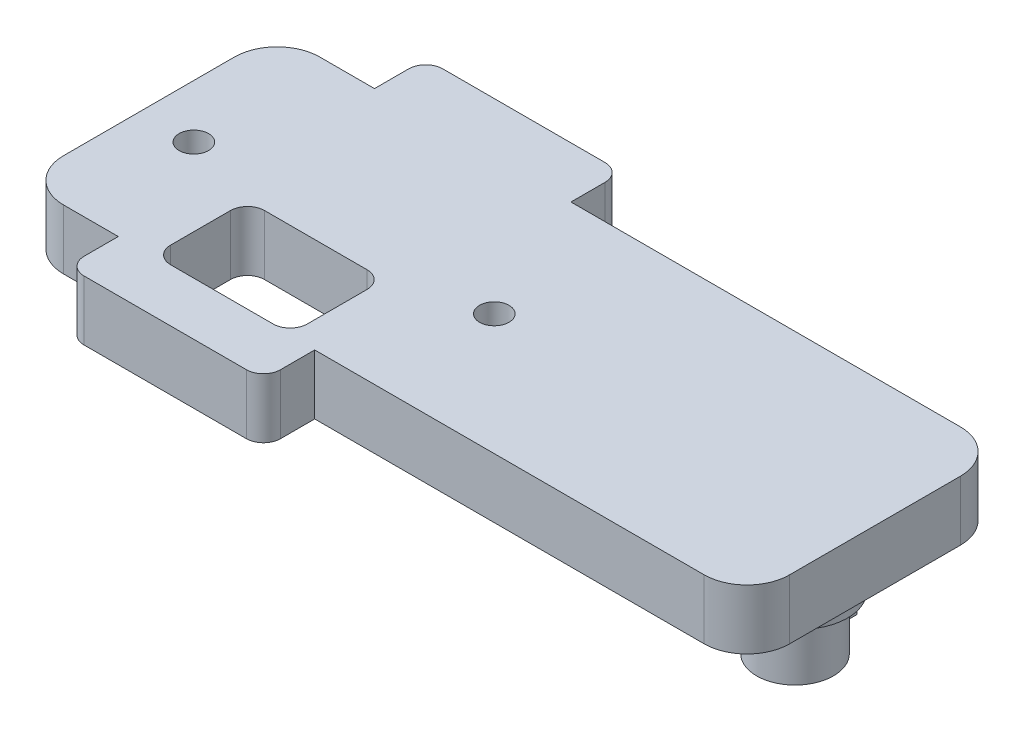
SolidWorks part; units mm, degrees
ref_plane "Front Plane" through (0, 0, 0) normal (0, 0, 1) x (1, 0, 0)
ref_plane "Top Plane" through (0, 0, 0) normal (0, 1, 0) x (1, 0, 0)
ref_plane "Right Plane" through (0, 0, 0) normal (1, 0, 0) x (0, 0, -1)
sketch "Sketch1" plane through (0, 0, 0) normal (0, 1, 0) x (1, 0, 0)
  line L1 (-33.413, 19.2228) -> (51.587, 19.2228)
  line L2 (-33.413, 19.2228) -> (-33.413, -10.7772)
  line L3 (-33.413, -10.7772) -> (51.587, -10.7772)
  line L4 (51.587, 19.2228) -> (51.587, -10.7772)
  dimension "D1" = 85
  dimension "D2" = 30
extrude "Boss-Extrude1" add sketch "Sketch1" along normal blind 7
ref_plane "Plane1" through (0, -1, 0) normal (0, -1, 0) x (-1, 0, 0)
sketch "Sketch2" plane through (0, -1, 0) normal (0, -1, 0) x (-1, 0, 0)
  line L0 (-51.587, 4.2228) -> (57.5711, 4.2228) construction
  line L1 (-41.1646, 1.3228) -> (-44.5646, 1.3228)
  line L2 (-41.1646, 1.3228) -> (-41.1646, 7.1228)
  line L3 (-41.1646, 7.1228) -> (-44.5646, 7.1228)
  line L4 (-44.5646, 1.3228) -> (-44.5646, 7.1228)
  line L5 (-51.587, -10.7772) -> (-51.587, 19.2228) construction
  line L6 (-42.8646, -10.7772) -> (-42.8646, 27.765) construction
  line L8 (33.413, -10.7772) -> (-51.587, -10.7772) construction
  dimension "D1" = 3.4
  dimension "D2" = 5.8
  dimension "D3" = 1.7
  dimension "D4" = 2.9
extrude "Boss-Extrude2" add sketch "Sketch2" along normal blind 6 separate body
shell "Shell1" thickness 1 removed face at (42.8646, -7, -4.2228) outward yes
sketch "Sketch3" plane through (0, 0, 0) normal (0, -1, 0) x (-1, 0, 0)
  line L0 (-42.8646, 1.3228) -> (-42.8646, 11.0227) construction
  line L1 (-44.5646, 1.3228) -> (-41.1646, 1.3228) construction
  line L2 (-41.1646, 4.2228) -> (-49.8164, 4.2228) construction
  line L3 (-41.1646, 1.3228) -> (-41.1646, 7.1228) construction
  point P9 (-42.8646, 4.2228)
sketch "Sketch4" plane through (0, 0, 0) normal (0, -1, 0) x (-1, 0, 0)
  circle A0 centre (-42.9099, 3.5376) radius 4.5
  circle A1 centre (-42.9099, 3.5376) radius 3.7
extrude "Boss-Extrude3" add sketch "Sketch4" along normal blind 10
sketch "Sketch5" plane through (0, 0, 0) normal (0, -1, 0) x (-1, 0, 0)
  circle A0 centre (-42.8646, 4.2228) radius 4.25
  circle A1 centre (-42.8646, 4.2228) radius 5.5
extrude "Boss-Extrude4" add sketch "Sketch5" along normal blind 4
fillet "Fillet1" radius 5 4 edges at (-33.413, 3.5, -19.2228) (-33.413, 3.5, 10.7772) (51.587, 3.5, -19.2228) (51.587, 3.5, 10.7772)
sketch "Sketch6" plane through (0, 0, 0) normal (0, -1, 0) x (-1, 0, 0)
  line L0 (28.413, -10.7772) -> (-46.587, -10.7772) construction
  line L1 (22.0125, -10.7772) -> (-0.9875, -10.7772)
  line L2 (22.0125, -10.7772) -> (22.0125, -16.7772)
  line L3 (22.0125, -16.7772) -> (-0.9875, -16.7772)
  line L4 (-0.9875, -10.7772) -> (-0.9875, -16.7772)
  line L5 (33.413, 4.2228) -> (44.2396, 4.2228) construction
  line L6 (33.413, 14.2228) -> (33.413, -5.7772) construction
  line L7 (22.0125, 25.2228) -> (-0.9875, 25.2228)
  line L8 (-0.9875, 19.2228) -> (-0.9875, 25.2228)
  line L9 (22.0125, 19.2228) -> (-0.9875, 19.2228)
  line L10 (22.0125, 19.2228) -> (22.0125, 25.2228)
  dimension "D1" = 6
  dimension "D2" = 23
extrude "Boss-Extrude5" add sketch "Sketch6" against normal up to surface (7 mm away) up to face at (9.087, 7, -4.2228)
sketch "Sketch7" plane through (0, 0, 0) normal (0, -1, 0) x (-1, 0, 0)
  line L0 (28.413, -10.7772) -> (22.0125, -10.7772) construction
  circle A0 centre (27.1643, 3.2228) radius 1.725
  circle A1 centre (-7.8353, 3.4015) radius 1.725
  point P4 (-7.8353, 0)
  dimension "D1" = 35
  dimension "D2" = 14
extrude "Cut-Extrude1" cut sketch "Sketch7" against normal up to surface (7 mm away) up to face at (-0.7127, 7, -4.2228)
fillet "Fillet2" radius 2 4 edges at (0.9875, 3.5, -25.2228) (-22.0125, 3.5, -25.2228) (0.9875, 3.5, 16.7772) (-22.0125, 3.5, 16.7772)
sketch "Sketch8" plane through (0, 0, 0) normal (0, -1, 0) x (-1, 0, 0)
  line L0 (1.0125, -16.7772) -> (20.0125, -16.7772) construction
  line L1 (18.0789, -10.5772) -> (2.0789, -10.5772)
  line L2 (18.0789, -10.5772) -> (18.0789, 0.4228)
  line L3 (18.0789, 0.4228) -> (2.0789, 0.4228)
  line L4 (2.0789, -10.5772) -> (2.0789, 0.4228)
  dimension "D1" = 16
  dimension "D2" = 11
  dimension "D3" = 6.2
extrude "Cut-Extrude2" cut sketch "Sketch8" against normal up to surface (7 mm away) up to face at (-27.1643, 7, -1.4978)
fillet "Fillet3" radius 2 4 edges at (-2.0789, 3.5, -0.4228) (-18.0789, 3.5, -0.4228) (-2.0789, 3.5, 10.5772) (-18.0789, 3.5, 10.5772)
